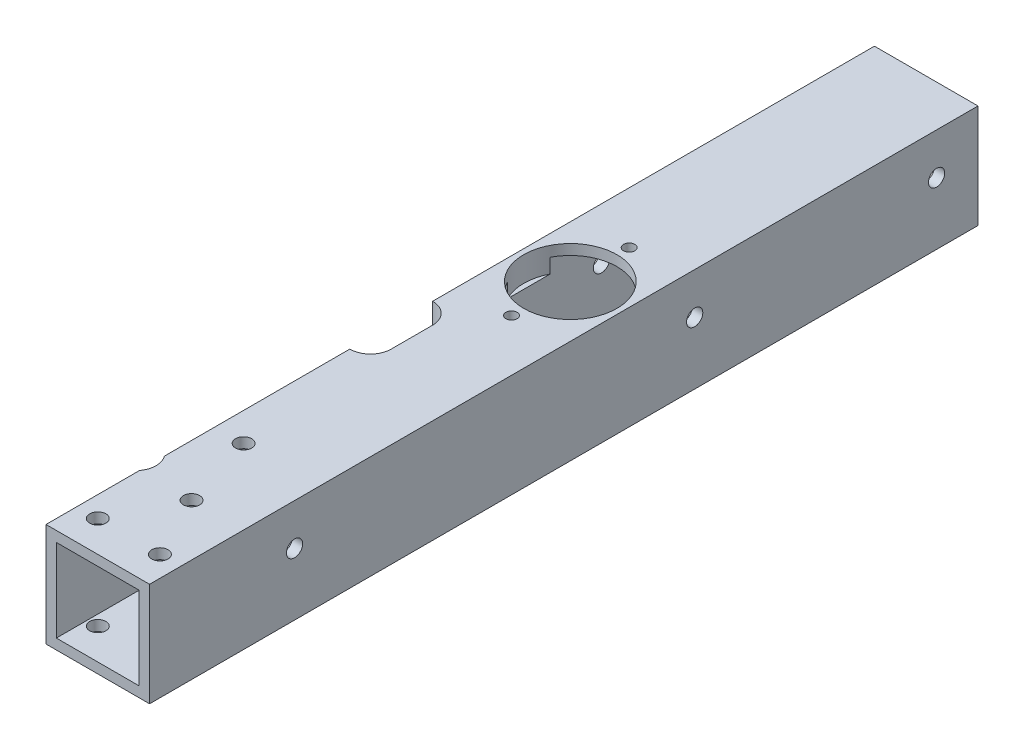
SolidWorks part; units mm, degrees
material "6061 Alloy"
ref_plane "Front Plane" through (0, 0, 0) normal (0, 0, 1) x (1, 0, 0)
ref_plane "Top Plane" through (0, 0, 0) normal (0, 1, 0) x (1, 0, 0)
ref_plane "Right Plane" through (0, 0, 0) normal (1, 0, 0) x (0, 0, -1)
sketch "Sketch1" plane through (0, 0, 0) normal (0, 0, 1) x (1, 0, 0)
  line L0 (-12.7, 12.7) -> (12.7, 12.7)
  line L2 (-15.875, 15.875) -> (15.875, 15.875)
  line L3 (-15.875, 15.875) -> (-15.875, -15.875)
  line L4 (-15.875, -15.875) -> (15.875, -15.875)
  line L5 (15.875, 15.875) -> (15.875, -15.875)
  line L10 (12.7, 12.7) -> (12.7, -12.7)
  line L11 (-12.7, -12.7) -> (12.7, -12.7)
  line L12 (-12.7, 12.7) -> (-12.7, -12.7)
  point P12 (0, 15.875)
  point P14 (15.875, 0)
  dimension "Wall Thickness" = 3.175
  dimension "Outside Width" = 31.75
  dimension "Outside Height" = 31.75
  dimension "Inside Height" = 25.4
  dimension "Inside Width" = 25.4
sketch "Sketch2" plane through (0, 0, 0) normal (1, 0, 0) x (0, 0, -1)
  line L0 (127, 0) -> (-127, 0)
  point P4 (0, 0)
  point P7 (-127, 0)
  point P10 (127, 0)
  dimension "Length" = 254
sketch "Sketch3" plane through (0, 0, 0) normal (0, 0, 1) x (1, 0, 0)
  line L21 (15.875, 15.875) -> (-15.875, 15.875)
  line L22 (15.875, -15.875) -> (15.875, 15.875)
  line L23 (-15.875, -15.875) -> (15.875, -15.875)
  line L24 (-15.875, 15.875) -> (-15.875, -15.875)
  line L25 (15.875, 15.875) -> (-15.875, 15.875)
  line L26 (15.875, -15.875) -> (15.875, 15.875)
  line L27 (-15.875, -15.875) -> (15.875, -15.875)
  line L28 (-15.875, 15.875) -> (-15.875, -15.875)
  line L29 (12.7, 12.7) -> (-12.7, 12.7)
  line L30 (12.7, -12.7) -> (12.7, 12.7)
  line L31 (-12.7, -12.7) -> (12.7, -12.7)
  line L32 (-12.7, 12.7) -> (-12.7, -12.7)
  line L33 (12.7, 12.7) -> (-12.7, 12.7)
  line L34 (12.7, -12.7) -> (12.7, 12.7)
  line L35 (-12.7, -12.7) -> (12.7, -12.7)
  line L36 (-12.7, 12.7) -> (-12.7, -12.7)
  dimension "D1" = 0
  dimension "D2" = 0
extrude "Boss-Extrude1" add sketch "Sketch3" along normal up to vertex (127 mm away) and the other way up to vertex (127 mm away) up to point (0, 0, 127) other way up to point (0, 0, -127)
sketch "Drawing Reference" plane through (0, 0, 0) normal (1, 0, 0) x (0, 0, -1)
  line L0 (-127, 0) -> (127, 0) construction
  line L1 (0, -15.875) -> (0, 15.875) construction
  line L2 (-127, -15.875) -> (127, -15.875) construction
  line L5 (-127, 15.875) -> (127, 15.875) construction
  point P7 (-104.14, 0)
  point P8 (104.14, 0)
  dimension "D1" = 22.86
sketch "Sketch4" plane through (0, 15.875, 0) normal (0, 1, 0) x (1, 0, 0)
  line L0 (0, -127) -> (0, -117.475) construction
  line L1 (15.875, -127) -> (-15.875, -127) construction
  line L2 (0, -117.475) -> (9.525, -117.475) construction
  line L3 (0, -117.475) -> (-9.525, -117.475) construction
  line L4 (0, -117.475) -> (0, 17.8816) construction
  line L5 (0, -117.475) -> (0, -98.2472) construction
  point P5 (-7.1119, -75.1713)
  dimension "D1" = 135.3566
  dimension "D2" = 19.05
  dimension "D3" = 9.525
hole_wizard "#10 Clearance Hole1" positions "Sketch5" profile "Sketch6" hole size "#10" standard "ANSI Inch" end condition through all
sketch "Sketch5" plane through (0, 15.875, 0) normal (0, 1, 0) x (1, 0, 0)
  point P0 (-9.525, -117.475)
  point P3 (9.525, -117.475)
  point P7 (0, -98.2472)
  point P10 (-7.1119, -75.1713)
sketch "Sketch6" plane through (-9.525, 15.875, 117.475) normal (1, 0, 0) x (0, 0, 1)
  line L0 (0, 0) -> (0, 31.75)
  line L1 (0, 31.75) -> (2.4892, 31.75)
  line L2 (2.4892, 31.75) -> (2.4892, 0)
  line L5 (2.4892, 0) -> (0, 0)
  line L11 (0, -6.35) -> (0, 107.95) construction
  dimension "Thru Hole Dia." = 4.9784
  dimension "Thru Hole Depth" = 31.75
sketch "Sketch7" plane through (0, 15.875, 0) normal (0, 1, 0) x (1, 0, 0)
  circle A0 centre (0, 17.8816) radius 14.2875
  dimension "D1" = 28.575
extrude "Cut-Extrude1" cut sketch "Sketch7" against normal blind 7.62
sketch "Sketch8" plane through (0, -15.875, 0) normal (0, -1, 0) x (1, 0, 0)
  circle A0 centre (0, -17.8816) radius 14.2875
  dimension "D1" = 28.575
extrude "Cut-Extrude2" cut sketch "Sketch8" against normal blind 7.62
sketch "Sketch9" plane through (0, -15.875, 0) normal (0, -1, 0) x (1, 0, 0)
  line L0 (-20.5727, 87.7258) -> (-42.1132, 74.2659) construction
  line L1 (-42.1132, 74.2659) -> (-15.875, 32.276) construction
  line L2 (-15.875, 127) -> (-15.875, -127) construction
  line L3 (-15.875, 32.276) -> (-9.099, 21.4322) construction
  line L4 (-15.875, 32.276) -> (-15.875, 27.5135) construction
  line L5 (-15.875, 27.5135) -> (-15.875, 14.8135) construction
  line L6 (-9.525, 27.5135) -> (-9.525, 14.8135)
  line L7 (-15.875, 8.4635) -> (-15.875, 33.8635)
  circle A0 centre (-15.875, 27.5135) radius 6.35 construction
  circle A1 centre (-15.875, 14.8135) radius 6.35 construction
  arc A2 (-15.875, 33.8635) -> (-9.525, 27.5135) centre (-15.875, 27.5135) cw
  arc A3 (-15.875, 8.4635) -> (-9.525, 14.8135) centre (-15.875, 14.8135) ccw
  dimension "D1" = 12.7
  dimension "D2" = 4.7625
extrude "Cut-Extrude3" cut sketch "Sketch9" against normal through all
sketch "Sketch10" plane through (15.875, 0, 0) normal (1, 0, 0) x (0, 0, -1)
  line L0 (-127, 3.175) -> (-82.55, 3.175) construction
  line L2 (-82.55, 3.175) -> (114.3, 3.175) construction
  line L3 (-127, -15.875) -> (-127, 3.175) construction
  line L4 (52.832, 3.175) -> (40.132, 3.175) construction
  line L5 (52.832, 434.0225) -> (52.832, -10.4775) construction
  dimension "D1" = 44.45
  dimension "D2" = 19.05
  dimension "D3" = 12.7
hole_wizard "#10 Clearance Hole2" positions "Sketch11" profile "Sketch12" hole size "#10" standard "ANSI Inch" end condition through all
sketch "Sketch11" plane through (15.875, 0, 0) normal (1, 0, 0) x (0, 0, -1)
  point P4 (-82.55, 3.175)
  point P7 (114.3, 3.175)
  point P12 (40.132, 3.175)
sketch "Sketch12" plane through (15.875, 3.175, 82.55) normal (0, 1, 0) x (0, 0, -1)
  line L0 (0, 0) -> (0, 31.75)
  line L1 (0, 31.75) -> (2.4892, 31.75)
  line L2 (2.4892, 31.75) -> (2.4892, 0)
  line L5 (2.4892, 0) -> (0, 0)
  line L11 (0, -6.35) -> (0, 107.95) construction
  dimension "Thru Hole Dia." = 4.9784
  dimension "Thru Hole Depth" = 31.75
sketch "Sketch13" plane through (0, -15.875, 0) normal (0, -1, 0) x (1, 0, 0)
  line L0 (-20.955, 94.5257) -> (-15.875, 94.5257) construction
  line L4 (-15.875, 127) -> (-15.875, 33.8635) construction
  circle A1 centre (-20.955, 94.5257) radius 6.35
  dimension "D1" = 5.08
extrude "Cut-Extrude4" cut sketch "Sketch13" against normal through all
sketch "Sketch14" plane through (0, -15.875, 0) normal (0, -1, 0) x (1, 0, 0)
  line L0 (0, -35.9156) -> (0, 0.1524) construction
  line L1 (0, 117.475) -> (0, -17.8816) construction
  line L2 (0, -17.8816) -> (5.4169, -17.8816) construction
  point P7 (0, -17.8816)
  dimension "D1" = 36.068
hole_wizard "Tap Drill for #8-32 Tap1" positions "Sketch17" profile "Sketch18" hole size "#8-32" standard "ANSI Inch"
sketch "Sketch17" plane through (0, 15.875, 0) normal (0, 1, 0) x (1, 0, 0)
  point P4 (0, 35.9156)
  point P9 (0, -0.1524)
sketch "Sketch18" plane through (0, 15.875, -35.9156) normal (1, 0, 0) x (0, 0, 1)
  line L0 (0, 0) -> (0, 6.1178)
  line L1 (0, 6.1178) -> (1.7272, 5.08)
  line L2 (1.7272, 5.08) -> (1.7272, 0)
  line L5 (1.7272, 0) -> (0, 0)
  line L10 (0, 6.1178) -> (-1.7272, 5.08) construction
  line L11 (0, -6.35) -> (0, 107.95) construction
  dimension "Hole Dia." = 3.4544
  dimension "Hole Depth" = 5.08
  dimension "Drill Angle" = 118
equation "\"D1@Drawing Reference\"=\"Outside Width@Sketch1\" * 0.72"
